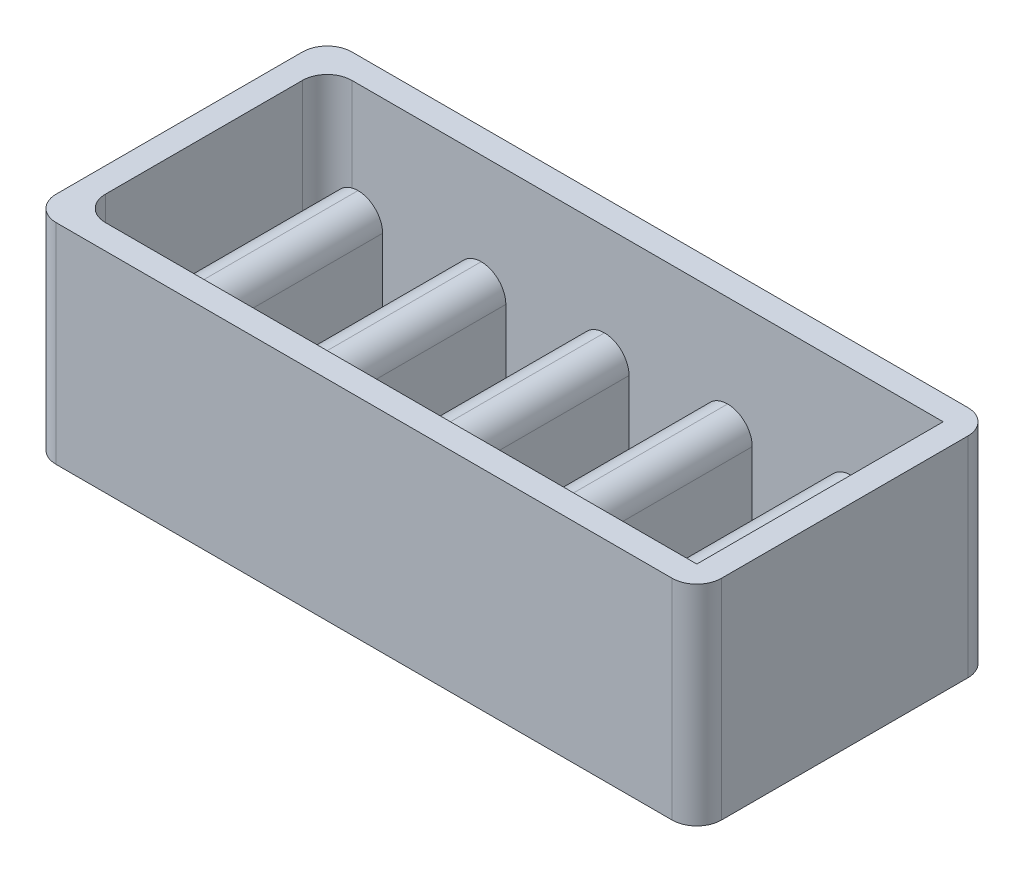
SolidWorks part; units mm, degrees
ref_plane "Alzado" through (0, 0, 0) normal (0, 0, 1) x (1, 0, 0)
ref_plane "Planta" through (0, 0, 0) normal (0, 1, 0) x (1, 0, 0)
ref_plane "Vista lateral" through (0, 0, 0) normal (1, 0, 0) x (0, 0, -1)
sketch "Croquis7" plane through (0, 0, 0) normal (0, 1, 0) x (1, 0, 0)
  line L1 (-25, 10) -> (25, 10)
  line L2 (-25, 10) -> (-25, -10)
  line L3 (-25, -10) -> (25, -10)
  line L4 (25, 10) -> (25, -10)
  line L5 (-25, 10) -> (25, -10) construction
  line L6 (-25, -10) -> (25, 10) construction
  line L7 (-27, 12) -> (27, 12)
  line L8 (-27, 12) -> (-27, -12)
  line L9 (-27, -12) -> (27, -12)
  line L10 (27, 12) -> (27, -12)
  line L11 (-27, 12) -> (27, -12) construction
  line L12 (-27, -12) -> (27, 12) construction
  point P0 (0, 0)
  point P6 (0, 0)
  dimension "D1" = 2
  dimension "D2" = 2
  dimension "D3" = 20
  dimension "D4" = 50
extrude "Saliente-Extruir7" add sketch "Croquis7" along normal blind 15
sketch "Croquis8" plane through (0, 0, 0) normal (0, -1, 0) x (1, 0, 0)
  line L1 (-27, 12) -> (27, 12)
  line L2 (-27, 12) -> (-27, -12)
  line L3 (-27, -12) -> (27, -12)
  line L4 (27, 12) -> (27, -12)
  line L5 (-27, 12) -> (27, -12) construction
  line L6 (-27, -12) -> (27, 12) construction
  point P0 (0, 0)
extrude "Saliente-Extruir8" add sketch "Croquis8" along normal blind 2
sketch "Croquis9" plane through (0, 0, 0) normal (0, 1, 0) x (1, 0, 0)
  line L0 (25, 2.5) -> (25, -2.5)
  line L1 (25, -10) -> (25, 10) construction
  line L2 (25, 0) -> (-20, 0) construction
  line L3 (25, 10) -> (-25, 10) construction
  line L4 (-22, 7.5) -> (-18, 7.5)
  line L5 (-22, 7.5) -> (-22, -7.5)
  line L6 (-22, -7.5) -> (-18, -7.5)
  line L7 (-18, 7.5) -> (-18, -7.5)
  line L8 (-22, 7.5) -> (-18, -7.5) construction
  line L9 (-22, -7.5) -> (-18, 7.5) construction
  line L10 (-25, -10) -> (25, -10) construction
  point P5 (25, 0)
  dimension "D1" = 5
  dimension "D2" = 45
  dimension "D3" = 4
  dimension "D4" = 15
  dimension "D5" = 10
  dimension "D6" = 10
extrude "Saliente-Extruir10" add sketch "Croquis9" along normal blind 10 contours L7 L4 L5 L6 region at (-20, 0, 0)
pattern_linear "MatrizL1" count 5 spacing 10 along (1, 0, 0) of "Saliente-Extruir10"
sketch "Croquis10" plane through (0, 0, 0) normal (0, 1, 0) x (1, 0, 0)
  line L0 (24.3251, 0) -> (25, 0) construction
  line L1 (-22, 1.916) -> (25, 1.916)
  line L2 (25, -10) -> (25, 10) construction
  line L3 (25, 1.916) -> (25, -1.916)
  line L4 (25, -1.916) -> (-22, -1.916)
  line L5 (25, -10) -> (25, 10) construction
  line L7 (25, 0) -> (-22, 0) construction
  line L8 (-22, 7.5) -> (-22, -7.5) construction
  line L9 (-22, 1.916) -> (-22, -1.916)
  line L10 (-22, 7.5) -> (-22, -7.5) construction
  point P13 (-22, 0)
extrude "Saliente-Extruir11" add sketch "Croquis10" along normal blind 3
fillet "Redondeo1" radius 2 10 edges at (23.5, 3, 1.916) (23.5, 3, -1.916) (15, 3, -1.916) (15, 3, 1.916) (5, 3, 1.916) (5, 3, -1.916) (-5, 3, 1.916) (-5, 3, -1.916) (-15, 3, -1.916) (-15, 3, 1.916)
fillet "Redondeo2" radius 2 2 edges at (-25, 7.5, 10) (-25, 7.5, -10)
fillet "Redondeo3" radius 2 10 edges at (22, 10, 0) (18, 10, 0) (12, 10, 0) (8, 10, 0) (2, 10, 0) (-18, 10, 0) (-22, 10, 0) (-12, 10, 0) (-2, 10, 0) (-8, 10, 0)
fillet "Redondeo4" radius 2 4 edges at (27, 6.5, -12) (27, 6.5, 12) (-27, 6.5, 12) (-27, 6.5, -12)
